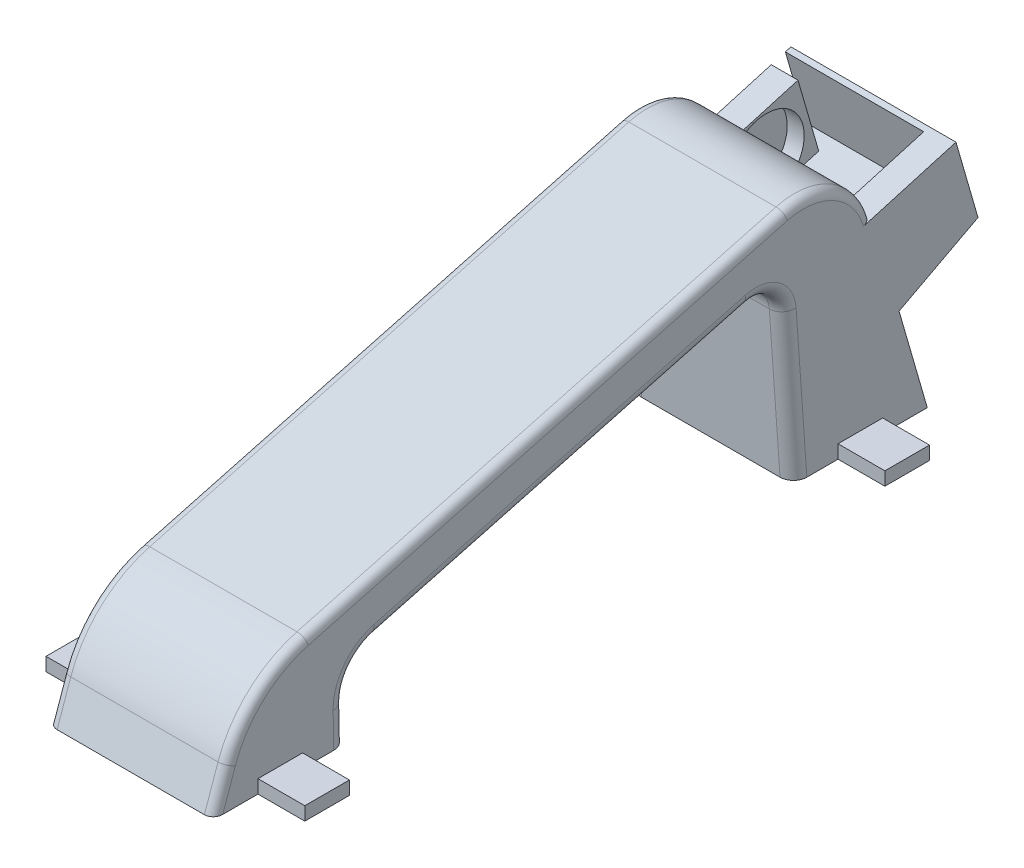
SolidWorks part; units mm, degrees
ref_plane "Front Plane" through (0, 0, 0) normal (0, 0, 1) x (1, 0, 0)
ref_plane "Top Plane" through (0, 0, 0) normal (0, 1, 0) x (1, 0, 0)
ref_plane "Right Plane" through (0, 0, 0) normal (1, 0, 0) x (0, 0, -1)
sketch "Sketch3" plane through (0, 0, 0) normal (1, 0, 0) x (0, 0, -1)
  line L0 (70.2156, -14.6169) -> (-37.1498, -43.3854)
  line L1 (-57.8901, -68.5284) -> (-54.8405, -59.8048)
  line L2 (-21.1992, -51.5348) -> (62.0724, -29.2222)
  line L4 (-27.8901, -68.5284) -> (-28.0453, -60.6408)
  line L8 (72.1099, -68.5284) -> (69.7171, -34.6709)
  line L9 (102.1099, -68.5284) -> (89.7292, -25.6347)
  line L11 (-57.8901, -68.5284) -> (-27.8901, -68.5284)
  line L12 (72.1099, -68.5284) -> (102.1099, -68.5284)
  arc A2 (69.7171, -34.6709) -> (62.0724, -29.2222) centre (63.6473, -35.0998) ccw
  arc A3 (89.7292, -25.6347) -> (70.2156, -14.6169) centre (74.3567, -30.0717) ccw
  arc A4 (-21.1992, -51.5348) -> (-28.0453, -60.6408) centre (-18.808, -60.4591) ccw
  arc A5 (-37.1498, -43.3854) -> (-54.8405, -59.8048) centre (-30.4672, -68.3253) ccw
  dimension "D1" = 16
  dimension "D2" = 12
  dimension "D3" = 30
  dimension "D4" = 160
  dimension "D5" = 100
  dimension "D7" = 30
extrude "Boss-Extrude2" add sketch "Sketch3" along normal mid plane 37
ref_plane "Plane1" through (0, 21.9359, -75.9987) normal (0, 0.2773, -0.9608) x (-1, 0, 0)
sketch "Sketch6" plane through (0, 21.9359, -75.9987) normal (0, 0.2773, -0.9608) x (-1, 0, 0)
  line L0 (18.5, -49.5125) -> (18.5, -73.5125)
  line L1 (18.5, -73.5125) -> (12.5, -73.5125)
  line L2 (-18.5, -94.1573) -> (18.5, -94.1573) construction
  line L3 (12.5, -73.5125) -> (12.5, -49.5125)
  line L4 (-18.5, -49.5125) -> (18.5, -49.5125) construction
  line L5 (12.5, -49.5125) -> (18.5, -49.5125)
  line L6 (0, -49.5125) -> (0, -94.1573) construction
  line L7 (-12.5, -73.5125) -> (-12.5, -49.5125)
  line L8 (-18.5, -73.5125) -> (-12.5, -73.5125)
  line L9 (-18.5, -49.5125) -> (-18.5, -73.5125)
  line L10 (-12.5, -49.5125) -> (-18.5, -49.5125)
  dimension "D1" = 6
  dimension "D2" = 24
extrude "Boss-Extrude3" add sketch "Sketch6" along normal blind 15
ref_plane "Plane2" through (-12.5, 0, 0) normal (1, 0, 0) x (0, 0, -1)
sketch "Sketch8" plane through (-12.5, 0, 0) normal (1, 0, 0) x (0, 0, -1)
  line L0 (89.7292, -25.6347) -> (102.1099, -68.5284) construction
  line L1 (89.7292, -25.6347) -> (96.3848, -48.6934) construction
  line L5 (104.1409, -21.475) -> (89.7292, -25.6347) construction
  circle A0 centre (97.0289, -32.8951) radius 8.5
  dimension "D1" = 5
  dimension "D2" = 17
  dimension "D3" = 9
extrude "Cut-Extrude1" cut sketch "Sketch8" against normal mid plane 7.6
fillet "Fillet1" radius 2 8 edges at (-18.5, -64.1666, 56.3653) (18.5, -64.1666, 56.3653) (-18.5, -49.4007, 48.0319) (-18.5, -29.0012, -16.5329) (-18.5, -16.1392, -82.2234) (18.5, -49.4007, 48.0319) (18.5, -29.0012, -16.5329) (18.5, -16.1392, -82.2234)
ref_plane "Plane3" through (0, -56.2176, -16.2264) normal (0, -0.9608, -0.2773) x (-1, 0, 0)
ref_axis "Axis1" through (-16.3, -32.8951, -97.0289) along (1, 0, 0)
sketch "Sketch11" plane through (0, -56.2176, -16.2264) normal (0, -0.9608, -0.2773) x (-1, 0, 0)
  line L1 (7.8166, 78.5392) -> (7.8166, 78.5805)
  line L2 (7.8166, 78.5805) -> (6.6814, 78.5805)
  line L3 (7.8166, 78.5392) -> (8.7, 78.5392)
  line L4 (8.7, 75.6011) -> (8.7, 79.1011) construction
  line L5 (8.7, 78.5392) -> (8.7, 79.1011)
  line L6 (8.7, 79.1011) -> (6.6814, 79.1011)
  line L7 (6.6814, 78.5805) -> (6.6814, 79.1011)
  line L8 (-18.5, 79.1011) -> (18.5, 79.1011) construction
  dimension "D1" = 0.8834
extrude "Cut-Extrude2" cut sketch "Sketch11" against normal mid plane 11.5
ref_plane "Plane6" through (12.5, 0, 0) normal (-1, 0, 0) x (0, 0, 1)
sketch "Sketch13" plane through (12.5, 0, 0) normal (-1, 0, 0) x (0, 0, 1)
  circle A0 centre (-97.0289, -32.8951) radius 1.5
  dimension "D1" = 3
extrude "Boss-Extrude4" add sketch "Sketch13" along normal blind 2.8
sketch "Sketch14" plane through (0, -56.2176, -16.2264) normal (0, -0.9608, -0.2773) x (-1, 0, 0)
  line L0 (5.309, 79.1011) -> (5.309, 77.2511)
  line L2 (5.309, 77.2511) -> (4.2831, 78.248)
  line L3 (4.2831, 78.248) -> (-8.728, 78.248)
  line L4 (-8.728, 78.248) -> (-9.6059, 79.1011)
  line L5 (5.309, 79.1011) -> (-9.6059, 79.1011)
extrude "Cut-Extrude3" cut sketch "Sketch14" against normal mid plane 10
sketch "Sketch15" plane through (-12.5, 0, 0) normal (1, 0, 0) x (0, 0, -1)
  line L0 (111.9495, -36.6549) -> (102.9796, -39.2439)
  line L2 (102.9796, -39.2439) -> (94.3123, -41.5132) construction
  line L3 (94.1313, -40.886) -> (96.3848, -48.6934) construction
  line L4 (104.4262, -38.6182) -> (110.383, -36.8989) construction
  line L5 (94.953, -41.3455) -> (94.3123, -41.5132)
  line L6 (94.3123, -41.5132) -> (95.7895, -46.6309)
  line L7 (95.7895, -46.6309) -> (113.4797, -37.3118)
  line L8 (113.4797, -37.3118) -> (108.542, -20.2047)
  line L9 (107.3045, -20.5619) -> (108.542, -20.2047)
  line L10 (104.1409, -21.475) -> (89.7292, -25.6347) construction
  line L11 (107.3045, -20.5619) -> (111.9495, -36.6549)
  arc A0 (102.9796, -39.2439) -> (94.953, -41.3455) centre (97.0289, -32.8951) cw
  dimension "D1" = 0.2
extrude "Boss-Extrude5" add sketch "Sketch15" along normal up to surface (25 mm away) up to face at (12.5, -31.3951, -97.0289)
sketch "Sketch16" plane through (-12.5, 0, 0) normal (1, 0, 0) x (0, 0, -1)
  line L6 (108.7859, -37.568) -> (109.3412, -39.4919)
  line L7 (111.9495, -36.6549) -> (108.7859, -37.568)
  line L8 (107.3045, -20.5619) -> (111.9495, -36.6549)
  line L9 (108.542, -20.2047) -> (107.3045, -20.5619)
  line L10 (113.4797, -37.3118) -> (108.542, -20.2047)
  line L11 (109.3412, -39.4919) -> (113.4797, -37.3118)
  line L12 (108.7859, -37.568) -> (109.3412, -39.4919)
  line L13 (111.9495, -36.6549) -> (108.7859, -37.568)
  line L14 (107.3045, -20.5619) -> (111.9495, -36.6549)
  line L15 (108.542, -20.2047) -> (107.3045, -20.5619)
  line L16 (113.4797, -37.3118) -> (108.542, -20.2047)
  line L17 (109.3412, -39.4919) -> (113.4797, -37.3118)
  dimension "D1" = 0
extrude "Boss-Extrude6" add sketch "Sketch16" against normal up to surface (6 mm away) up to face at (-18.5, -46.994, -36.8791)
sketch "Sketch17" plane through (12.5, 0, 0) normal (-1, 0, 0) x (0, 0, 1)
  line L6 (-108.7859, -37.568) -> (-111.9495, -36.6549)
  line L7 (-109.3412, -39.4919) -> (-108.7859, -37.568)
  line L8 (-113.4797, -37.3118) -> (-109.3412, -39.4919)
  line L9 (-108.542, -20.2047) -> (-113.4797, -37.3118)
  line L10 (-107.3045, -20.5619) -> (-108.542, -20.2047)
  line L11 (-111.9495, -36.6549) -> (-107.3045, -20.5619)
  line L13 (-109.3412, -39.4919) -> (-104.1409, -21.475)
  line L14 (-113.4797, -37.3118) -> (-109.3412, -39.4919)
  line L15 (-108.542, -20.2047) -> (-113.4797, -37.3118)
  line L16 (-104.1409, -21.475) -> (-108.542, -20.2047)
  dimension "D1" = 0
extrude "Boss-Extrude7" add sketch "Sketch17" against normal up to surface (6 mm away) up to face at (18.5, -46.994, -36.8791)
sketch "Sketch21" plane through (0, 0, 0) normal (1, 0, 0) x (0, 0, -1)
  line L0 (72.1099, -68.5284) -> (102.1099, -68.5284) construction
  line L1 (-55.7714, -68.5284) -> (-27.8901, -68.5284) construction
  line L2 (-47.8901, -68.5284) -> (-37.8901, -68.5284)
  line L3 (82.1099, -68.5284) -> (92.1099, -68.5284)
  line L4 (82.1099, -68.5284) -> (82.1099, -65.5284)
  line L5 (82.1099, -65.5284) -> (92.1099, -65.5284)
  line L6 (92.1099, -68.5284) -> (92.1099, -65.5284)
  line L11 (-47.8901, -68.5284) -> (-47.8901, -65.5284)
  line L12 (-47.8901, -65.5284) -> (-37.8901, -65.5284)
  line L13 (-37.8901, -68.5284) -> (-37.8901, -65.5284)
  dimension "D1" = 10
  dimension "D2" = 10
  dimension "D3" = 3
  dimension "D4" = 10
  dimension "D5" = 3
  dimension "D6" = 10
extrude "Boss-Extrude8" add sketch "Sketch21" along normal mid plane 58
sketch "Sketch25" plane through (12.5, 0, 0) normal (-1, 0, 0) x (0, 0, 1)
  line L0 (-96.3848, -48.6934) -> (-110.7965, -44.5337)
  line L2 (-110.7965, -44.5337) -> (-109.3412, -39.4919)
  line L4 (-96.3848, -48.6934) -> (-95.7895, -46.6309)
  line L5 (-113.4797, -37.3118) -> (-109.3412, -39.4919) construction
  line L6 (-102.1099, -68.5284) -> (-96.3848, -48.6934) construction
  line L7 (-109.3412, -39.4919) -> (-95.7895, -46.6309)
extrude "Cut-Extrude4" cut sketch "Sketch25" against normal mid plane 80.7
fillet "Fillet3" radius 3 10 edges at (18.5, -64.5846, 27.9677) (18.5, -54.907, 26.1928) (18.5, -40.3785, -20.4366) (18.5, -30.1447, -67.179) (18.5, -51.5996, -70.9135) (-18.5, -51.5996, -70.9135) (-18.5, -30.1447, -67.179) (-18.5, -54.907, 26.1928) (-18.5, -64.5846, 27.9677) (-18.5, -40.3785, -20.4366)
ref_plane "Plane7" through (-18.5, 0, 0) normal (-1, 0, 0) x (0, 0, 1)
sketch "Sketch24" plane through (-18.5, 0, 0) normal (-1, 0, 0) x (0, 0, 1)
  line L0 (-95.6257, -50.1523) -> (-93.4071, -42.4661)
  line L1 (-108.7859, -37.568) -> (-104.1409, -21.475) construction
  line L2 (-93.4071, -42.4661) -> (-92.4464, -42.7434)
  line L3 (-92.4464, -42.7434) -> (-94.6649, -50.4296)
  line L4 (-94.6649, -50.4296) -> (-95.6257, -50.1523)
  line L5 (-102.1099, -68.5284) -> (-95.7895, -46.6309) construction
  line L6 (-90.997, -41.5082) -> (-94.6826, -54.2774) construction
  line L8 (-90.4287, -43.3257) -> (-92.6472, -51.012)
  line L9 (-89.468, -43.603) -> (-90.4287, -43.3257)
  line L10 (-91.6865, -51.2893) -> (-89.468, -43.603)
  line L11 (-92.6472, -51.012) -> (-91.6865, -51.2893)
  dimension "D1" = 8
  dimension "D2" = 1
  dimension "D3" = 1.05
extrude "Boss-Extrude9" add sketch "Sketch24" along normal blind 0.72
ref_plane "Plane8" through (-19.22, 0, 0) normal (-1, 0, 0) x (0, 0, 1)
sketch "Sketch26" plane through (-19.22, 0, 0) normal (-1, 0, 0) x (0, 0, 1)
  line L0 (-93.4071, -42.4661) -> (-89.468, -43.603)
  line L1 (-89.468, -43.603) -> (-91.6865, -51.2893)
  line L2 (-91.6865, -51.2893) -> (-95.6257, -50.1523)
  line L3 (-95.6257, -50.1523) -> (-93.4071, -42.4661)
extrude "Boss-Extrude10" add sketch "Sketch26" along normal blind 0.5
